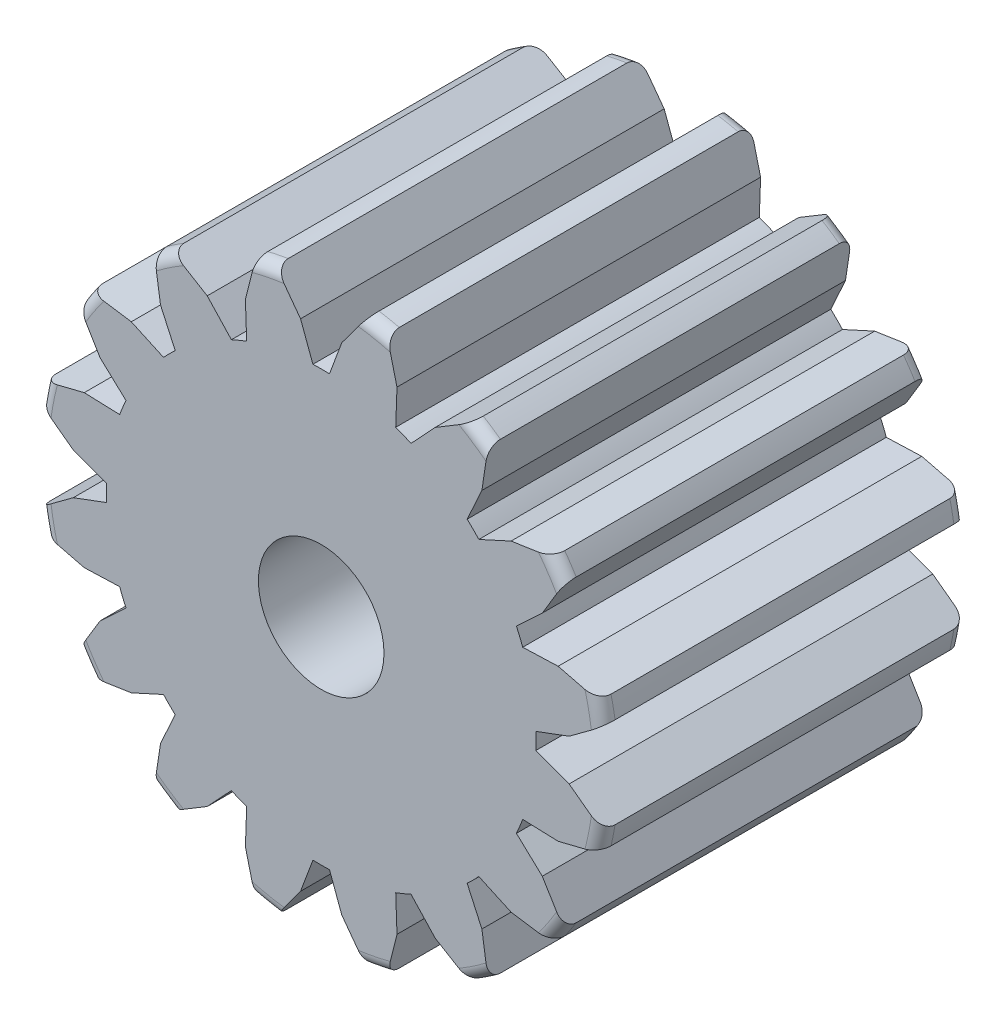
SolidWorks part; units mm, degrees
material "Aleación 1060"
ref_plane "Alzado" through (0, 0, 0) normal (0, 0, 1) x (1, 0, 0)
ref_plane "Planta" through (0, 0, 0) normal (0, 1, 0) x (1, 0, 0)
ref_plane "Vista lateral" through (0, 0, 0) normal (1, 0, 0) x (0, 0, -1)
sketch "Croquis1" plane through (0, 0, 0) normal (0, 0, 1) x (1, 0, 0)
  circle A0 centre (0, 0) radius 3.45
  dimension "D1" = 6.9
extrude "Saliente-Extruir1" add sketch "Croquis1" along normal blind 4.4
sketch "Croquis2" plane through (0, 0, 4.4) normal (0, 0, 1) x (1, 0, 0)
  line L0 (0, 0) -> (0, 4.4326) construction
  line L1 (0.55, 3.7) -> (-0.55, 3.7)
  line L2 (-0.55, 3.7) -> (-0.55, 3.4059)
  line L3 (-0.55, 3.4059) -> (-0.25, 3)
  line L4 (-0.25, 3) -> (-0.1, 2.5981)
  line L5 (0.55, 3.7) -> (0.55, 3.4059)
  line L6 (0.55, 3.4059) -> (0.25, 3)
  line L7 (0.25, 3) -> (0.1, 2.5981)
  circle A0 centre (0, 0) radius 2.6
  circle A1 centre (0, 0) radius 3.45 construction
  circle A2 centre (0, 0) radius 0.76
  point P15 (0, 3.7)
  circle M5 centre (0, 0) radius 3.45
  dimension "D1" = 5.2
  dimension "D7" = 1.52
  dimension "D2" = 0.55
  dimension "D3" = 0.1
  dimension "D4" = 3.7
  dimension "D5" = 3
  dimension "D6" = 0.25
extrude "Cortar-Extruir1" cut sketch "Croquis2" against normal blind 4.4 contours L0 L5 L1 M5 | L0 L1 L2 M5 | A0 L0 L3 L4 M5 | L0 A0 L7 L6 M5 region at (-0.1763, 3.1281, 4.4) region at (0.1763, 3.1281, 4.4) region at (-0.2826, 3.5673, 4.4) region at (0.2826, 3.5673, 4.4)
fillet "Redondeo1" radius 0.15 2 edges at (0, -3.45, 0) (0, -3.45, 4.4)
pattern_circular "MatrizC1" count 16 over 360 about axis through (0, 0, 4.4) along (0, 0, -1) of "Cortar-Extruir1"
extrude "Cortar-Extruir2" cut sketch "Croquis2<3>" against normal blind 4.4 contours A2 region at (0, 0, 4.4)
sketch "Croquis2<3>" plane through (0, 0, 4.4) normal (0, 0, 1) x (1, 0, 0) same geometry as "Croquis2"
